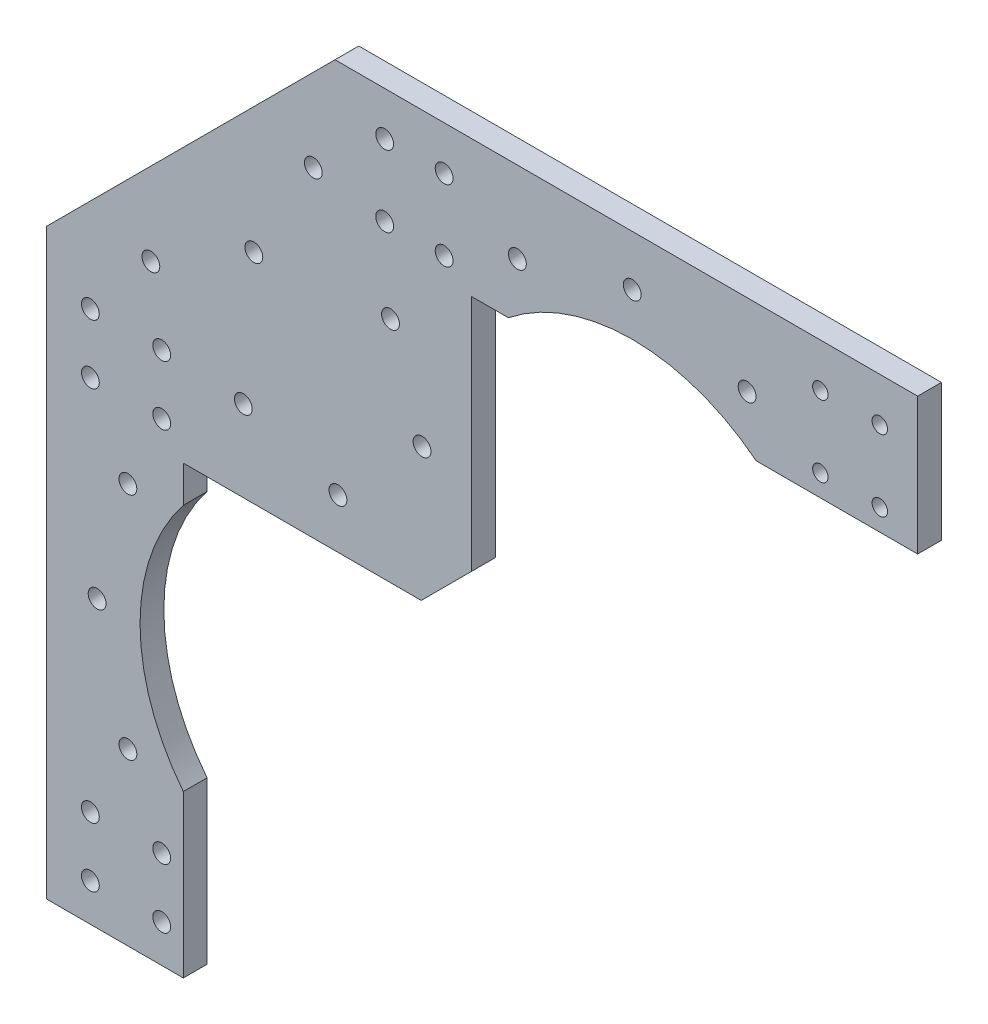
SolidWorks part; units mm, degrees
ref_plane "Front Plane" through (0, 0, 0) normal (0, 0, 1) x (1, 0, 0)
ref_plane "Top Plane" through (0, 0, 0) normal (0, 1, 0) x (1, 0, 0)
ref_plane "Right Plane" through (0, 0, 0) normal (1, 0, 0) x (0, 0, -1)
sketch "Sketch1" plane through (0, 0, 0) normal (0, 0, 1) x (1, 0, 0)
  line L0 (0, 0) -> (0, 75.5) construction
  line L1 (-98.5, -48) -> (-75.5, -48)
  line L2 (-98.5, -48) -> (-98.5, 49.9924)
  line L4 (-75.5, -48) -> (-75.5, 27) construction
  line L5 (-49.9924, 98.5) -> (48, 98.5)
  line L7 (-27, 75.5) -> (48, 75.5) construction
  line L8 (48, 98.5) -> (48, 75.5)
  line L9 (0, 0) -> (-75.5, 0) construction
  line L10 (-27, 75.5) -> (-75.5, 27) construction
  line L11 (-75.5, 75.5) -> (-27, 75.5) construction
  line L12 (-75.5, 27) -> (-75.5, 75.5) construction
  line L13 (-49.9924, 98.5) -> (-98.5, 49.9924)
  line L14 (-98.5, 98.5) -> (-49.9924, 98.5) construction
  line L15 (-98.5, 49.9924) -> (-98.5, 98.5) construction
  line L16 (-20.8425, 75.5) -> (-27, 75.5)
  line L17 (20.8425, 75.5) -> (48, 75.5)
  line L18 (-75.5, 27) -> (-75.5, 20.8425)
  line L19 (-75.5, -48) -> (-75.5, -20.8425)
  line L20 (-75.5, 20.8425) -> (-75.5, -20.8425) construction
  line L21 (-20.8425, 75.5) -> (20.8425, 75.5) construction
  line L22 (-75.5, 27) -> (-35.4853, 27)
  line L23 (-27, 35.4853) -> (-27, 75.5)
  line L24 (-35.4853, 27) -> (-27, 35.4853)
  arc A0 (20.8425, 75.5) -> (-20.8425, 75.5) centre (0, 49.3) ccw
  arc A1 (-75.5, 20.8425) -> (-75.5, -20.8425) centre (-49.3, 0) ccw
  dimension "D6" = 33.4791
  dimension "D1" = 135
  dimension "D2" = 23
  dimension "D3" = 75.5
  dimension "D4" = 48
  dimension "D5" = 105
  dimension "D7" = 49.3
  dimension "D8" = 27
  dimension "D9" = 12
extrude "Boss-Extrude1" add sketch "Sketch1" along normal blind 4
ref_axis "Axis1" through (0, 0, -0.2) along (0, 0, 1)
sketch "Sketch3" plane through (0, 0, 4) normal (0, 0, 1) x (1, 0, 0)
  line L0 (-91.1351, 41.6359) -> (-91.1351, 31.6359) construction
  line L1 (-91.1351, -31.6359) -> (-91.1351, -41.6359) construction
  line L2 (-91.1351, -31.6359) -> (-79.1351, -31.6359) construction
  line L3 (-79.1351, -31.6359) -> (-79.1351, -41.6359) construction
  line L4 (-91.1351, -41.6359) -> (-79.1351, -41.6359) construction
  line L5 (-91.1351, 41.6359) -> (-79.1351, 41.6359) construction
  line L6 (-79.1351, 41.6359) -> (-79.1351, 31.6359) construction
  line L7 (-91.1351, 31.6359) -> (-79.1351, 31.6359) construction
  line L8 (31.6359, 91.1351) -> (31.6359, 79.1351) construction
  line L9 (31.6359, 91.1351) -> (41.6359, 91.1351) construction
  line L10 (41.6359, 91.1351) -> (41.6359, 79.1351) construction
  line L11 (31.6359, 79.1351) -> (41.6359, 79.1351) construction
  line L12 (-31.6359, 91.1351) -> (-31.6359, 79.1351) construction
  line L13 (-31.6359, 91.1351) -> (-41.6359, 91.1351) construction
  line L14 (-41.6359, 91.1351) -> (-41.6359, 79.1351) construction
  line L15 (-31.6359, 79.1351) -> (-41.6359, 79.1351) construction
  circle A0 centre (-91.1351, -41.6359) radius 1.5
  circle A1 centre (-91.1351, -31.6359) radius 1.5
  circle A2 centre (-79.1351, -31.6359) radius 1.5
  circle A3 centre (-79.1351, -41.6359) radius 1.5
  circle A4 centre (-91.1351, 31.6359) radius 1.5
  circle A5 centre (-91.1351, 41.6359) radius 1.5
  circle A6 centre (-79.1351, 41.6359) radius 1.5
  circle A7 centre (-79.1351, 31.6359) radius 1.5
  circle A8 centre (31.6359, 79.1351) radius 1.3
  circle A9 centre (31.6359, 91.1351) radius 1.3
  circle A10 centre (41.6359, 91.1351) radius 1.3
  circle A11 centre (41.6359, 79.1351) radius 1.3
  circle A12 centre (-31.6359, 79.1351) radius 1.5
  circle A13 centre (-31.6359, 91.1351) radius 1.5
  circle A14 centre (-41.6359, 91.1351) radius 1.5
  circle A15 centre (-41.6359, 79.1351) radius 1.5
  dimension "D1" = 3
  dimension "D2" = 3
  dimension "D3" = 2.6
  dimension "D4" = 3
extrude "Cut-Extrude1" cut sketch "Sketch3" against normal blind 10
sketch "Sketch4" plane through (0, 0, 4) normal (0, 0, 1) x (1, 0, 0)
  line L0 (0, 0) -> (0, 90) construction
  line L1 (0, 0) -> (-63.6396, 63.6396) construction
  line L2 (0, 0) -> (-90, 0) construction
  line L3 (-84.8236, 19.3185) -> (-90, 0) construction
  line L4 (-90, 0) -> (-84.8236, -19.3185) construction
  line L5 (-80.9601, 53.6396) -> (-63.6396, 63.6396) construction
  line L6 (-63.6396, 63.6396) -> (-69.6582, 69.6582) construction
  line L7 (-19.3185, 84.8236) -> (0, 90) construction
  line L8 (-65.4074, 40.6586) -> (-40.6586, 65.4074) construction
  line L9 (-35.3553, 49.4975) -> (-49.4975, 35.3553) construction
  circle A0 centre (-90, 0) radius 1.5
  circle A1 centre (-63.6396, 63.6396) radius 1.5
  circle A2 centre (0, 90) radius 1.5
  circle A3 centre (-80.9601, 53.6396) radius 1.5
  circle A4 centre (-53.6396, 80.9601) radius 1.5
  circle A5 centre (19.3185, 84.8236) radius 1.5
  circle A6 centre (-19.3185, 84.8236) radius 1.5
  circle A7 centre (-84.8236, 19.3185) radius 1.5
  circle A8 centre (-84.8236, -19.3185) radius 1.5
  circle A9 centre (-40.6586, 65.4074) radius 1.5
  circle A10 centre (-65.4074, 40.6586) radius 1.5
  circle A11 centre (-49.4975, 35.3553) radius 1.5
  circle A12 centre (-35.3553, 49.4975) radius 1.5
  dimension "D2" = 3
  dimension "D1" = 45
  dimension "D3" = 90
  dimension "D4" = 75
  dimension "D5" = 20
  dimension "D6" = 90
  dimension "D7" = 75
  dimension "D8" = 75
  dimension "D9" = 35
  dimension "D10" = 20
  dimension "D11" = 15
  dimension "D12" = 15
extrude "Cut-Extrude2" cut sketch "Sketch4" against normal through all
equation "\"EyeDiameter\" = 35"
equation "\"BasePlaneDistance\" = \"EyeDiameter\"/2+19.84"
equation "\"EyeClearance\" = 2"
equation "\"L2Thickness\" = 8"
equation "\"L2_ID\" = 20"
equation "\"D3@Sketch1\"= \"BasePlaneDistance\" + 38.16"
